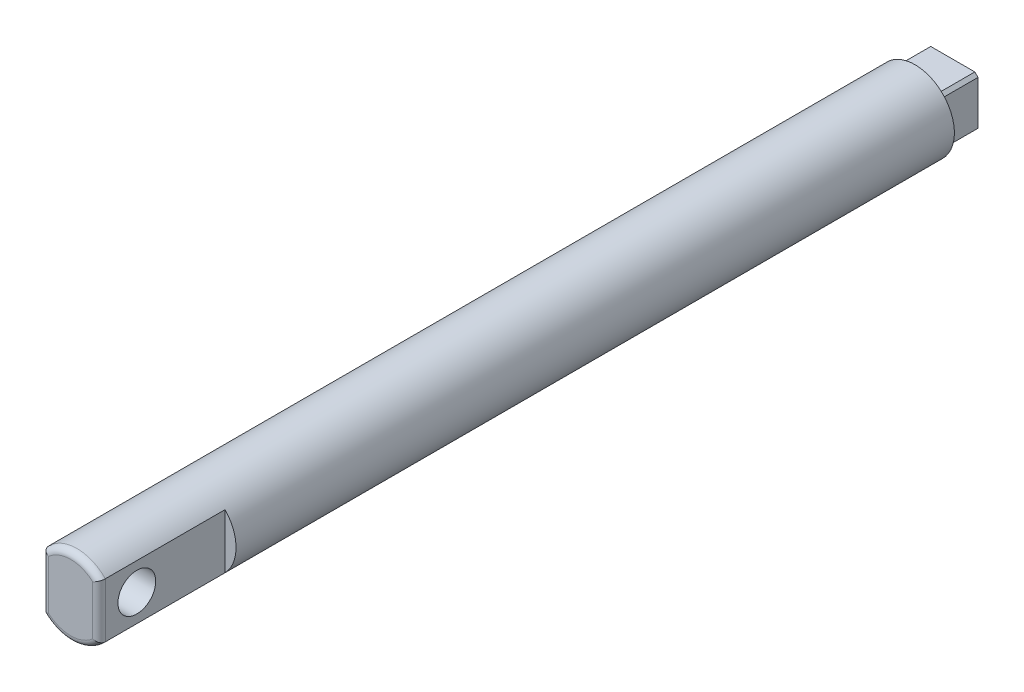
SolidWorks part; units mm, degrees
material "1023 Carbon Steel Sheet (SS)"
ref_plane "Plano frontal" through (0, 0, 0) normal (0, 0, 1) x (1, 0, 0)
ref_plane "Plano superior" through (0, 0, 0) normal (0, 1, 0) x (1, 0, 0)
ref_plane "Plano direito" through (0, 0, 0) normal (1, 0, 0) x (0, 0, -1)
sketch "Sketch1" plane through (0, 0, 0) normal (0, 0, 1) x (1, 0, 0)
  circle A0 centre (0, 0) radius 12.5
  dimension "D1" = 25
extrude "Boss-Extrude1" add sketch "Sketch1" along normal blind 280
sketch "Sketch2" plane through (0, 0, 280) normal (0, 0, 1) x (1, 0, 0)
  line L0 (-9, 8.6747) -> (-9, -8.6747)
  line L1 (9, 8.6747) -> (9, -8.6747)
  circle A0 centre (0, 0) radius 12.5 construction
  circle A1 centre (0, 0) radius 12.5
  circle A2 centre (0, 0) radius 12.5
  circle M4 centre (0, 0) radius 12.5
  dimension "D2" = 18
  dimension "D1" = 0
extrude "Cut-Extrude1" cut sketch "Sketch2" against normal blind 40 contours L0 M4 | L1 M4 region at (-10.4183, 0, 280) region at (10.4183, 0, 280)
sketch "Sketch3" plane through (-9, 0, 0) normal (-1, 0, 0) x (0, 0, 1)
  line L0 (268, 0) -> (280, 0) construction
  line L1 (280, 8.6747) -> (280, -8.6747) construction
  circle A0 centre (268, 0) radius 6
  dimension "D1" = 12
  dimension "D2" = 12
extrude "Cut-Extrude2" cut sketch "Sketch3" against normal through all
fillet "Fillet1" radius 2 4 edges at (0, 12.5, 280) (9, 0, 280) (0, -12.5, 280) (-9, 0, 280)
sketch "Sketch4" plane through (0, 0, 0) normal (0, 0, -1) x (-1, 0, 0)
  line L1 (8, -8) -> (-8, -8)
  line L2 (8, -8) -> (8, 8)
  line L3 (8, 8) -> (-8, 8)
  line L4 (-8, -8) -> (-8, 8)
  line L5 (8, -8) -> (-8, 8) construction
  line L6 (8, 8) -> (-8, -8) construction
  circle A2 centre (0, 0) radius 12.5
  circle A3 centre (0, 0) radius 12.5
  point P0 (0, 0)
  circle M6 centre (0, 0) radius 12.5
  dimension "D2" = 16
  dimension "D1" = 0
extrude "Cut-Extrude3" cut sketch "Sketch4" against normal blind 12 contours L3 M6 | L4 M6 | L1 M6 | L2 M6 region at (12.1464, 0, 0)
hole_wizard "M6 Tapped Hole1" positions "Sketch7" profile "Sketch5" tap size "M6" standard "DIN"
sketch "Sketch7" plane through (0, 0, 0) normal (0, 0, -1) x (-1, 0, 0)
  point P0 (0, 0)
sketch "Sketch5" plane through (0, 0, 0) normal (1, 0, 0) x (0, 1, 0)
  line L0 (0, 0) -> (0, 16.5022)
  line L1 (0, 16.5022) -> (2.5, 15)
  line L2 (2.5, 15) -> (2.5, 0)
  line L5 (2.5, 0) -> (0, 0)
  line L10 (0, 16.5022) -> (-2.5, 15) construction
  line L11 (0, -6.35) -> (0, 107.95) construction
  dimension "Tap Drill Dia." = 5
  dimension "Tap Drill Depth" = 15
  dimension "Drill Angle" = 118
cosmetic thread "Hole Thread1" parameters "D1"=12, "D2"=6
chamfer "Chamfer1" distance 1 angle 45 4 edges at (-8, -8, 6) (-8, 8, 6) (8, -8, 6) (8, 8, 6)
ref_axis "Axis1" through (0, 0, 317.7619) along (0, 0, -1)
ref_axis "Axis2" through (9, 0, 268) along (-1, 0, 0)
ref_point "Point5"
